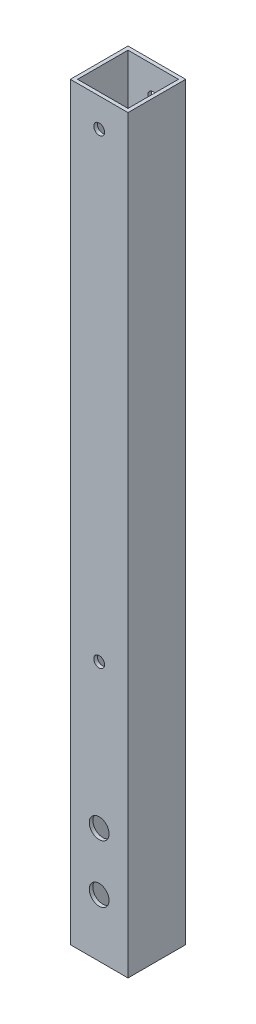
SolidWorks part; units mm, degrees
ref_plane "Front Plane" through (0, 0, 0) normal (0, 0, 1) x (1, 0, 0)
ref_plane "Top Plane" through (0, 0, 0) normal (0, 1, 0) x (1, 0, 0)
ref_plane "Right Plane" through (0, 0, 0) normal (1, 0, 0) x (0, 0, -1)
sketch "Sketch1" plane through (0, 0, 0) normal (0, 1, 0) x (1, 0, 0)
  line L1 (12.7, -12.7) -> (-12.7, -12.7)
  line L2 (12.7, -12.7) -> (12.7, 12.7)
  line L3 (12.7, 12.7) -> (-12.7, 12.7)
  line L4 (-12.7, -12.7) -> (-12.7, 12.7)
  line L5 (12.7, -12.7) -> (-12.7, 12.7) construction
  line L6 (12.7, 12.7) -> (-12.7, -12.7) construction
  line L7 (11.1125, -11.1125) -> (-11.1125, -11.1125)
  line L8 (11.1125, -11.1125) -> (11.1125, 11.1125)
  line L9 (11.1125, 11.1125) -> (-11.1125, 11.1125)
  line L10 (-11.1125, -11.1125) -> (-11.1125, 11.1125)
  line L11 (11.1125, -11.1125) -> (-11.1125, 11.1125) construction
  line L12 (11.1125, 11.1125) -> (-11.1125, -11.1125) construction
  point P0 (0, 0)
  point P6 (0, 0)
  dimension "D1" = 25.4
  dimension "D2" = 1.5875
extrude "Boss-Extrude1" add sketch "Sketch1" along normal blind 330.2
sketch "Sketch2" plane through (0, 0, 12.7) normal (0, 0, 1) x (1, 0, 0)
  line L0 (0, 330.2) -> (0, 0) construction
  line L1 (-12.7, 330.2) -> (12.7, 330.2) construction
  line L2 (-12.7, 0) -> (12.7, 0) construction
  circle A0 centre (0, 25.4) radius 4.3656
  circle A1 centre (0, 50.8) radius 4.3656
  circle A2 centre (0, 317.5) radius 2.3813
  circle A3 centre (0, 114.3) radius 2.3812
  dimension "D1" = 8.7312
  dimension "D2" = 4.7625
  dimension "D3" = 12.7
  dimension "D4" = 203.2
  dimension "D5" = 25.4
  dimension "D6" = 25.4
extrude "Cut-Extrude1" cut sketch "Sketch2" against normal up to surface (25.4 mm away) up to face at (0, 165.1, -12.7)
